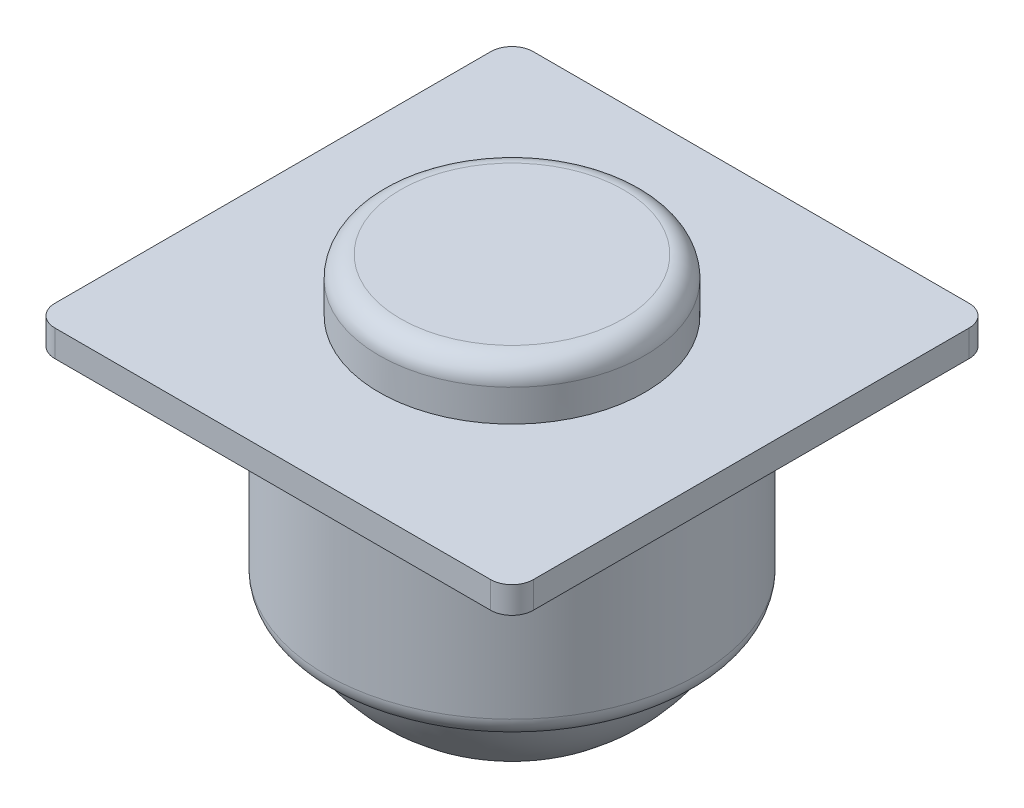
SolidWorks part; units mm, degrees
ref_plane "Front Plane" through (0, 0, 0) normal (0, 0, 1) x (1, 0, 0)
ref_plane "Top Plane" through (0, 0, 0) normal (0, 1, 0) x (1, 0, 0)
ref_plane "Right Plane" through (0, 0, 0) normal (1, 0, 0) x (0, 0, -1)
sketch "Sketch1" plane through (0, 0, 0) normal (0, 1, 0) x (1, 0, 0)
  line L1 (-14.2875, -14.2875) -> (14.2875, -14.2875)
  line L2 (-14.2875, -14.2875) -> (-14.2875, 14.2875)
  line L3 (-14.2875, 14.2875) -> (14.2875, 14.2875)
  line L4 (14.2875, -14.2875) -> (14.2875, 14.2875)
  line L5 (-14.2875, -14.2875) -> (14.2875, 14.2875) construction
  line L6 (-14.2875, 14.2875) -> (14.2875, -14.2875) construction
  point P0 (0, 0)
  dimension "D1" = 28.575
extrude "Boss-Extrude1" add sketch "Sketch1" along normal blind 1.5875
sketch "Sketch2" plane through (0, 1.5875, 0) normal (0, 1, 0) x (1, 0, 0)
  circle A0 centre (0, 0) radius 7.9375
  dimension "D1" = 15.875
extrude "Boss-Extrude2" add sketch "Sketch2" along normal blind 3.175
sketch "Sketch3" plane through (0, 0, 0) normal (0, -1, 0) x (1, 0, 0)
  circle A0 centre (0, 0) radius 11.1125
  dimension "D1" = 22.225
extrude "Boss-Extrude3" add sketch "Sketch3" along normal blind 12.7
fillet "Fillet1" radius 1.27 2 edges at (0, -12.7, -11.1125) (0, 4.7625, 7.9375)
dome "Dome1" faces to dome 1 distance 6.35 reverse direction no elliptical dome no face at (0, -12.7, -9.8425) parameters "D1"=6.35
fillet "Fillet2" radius 1.27 4 edges at (-14.2875, 0.7937, -14.2875) (14.2875, 0.7937, -14.2875) (14.2875, 0.7937, 14.2875) (-14.2875, 0.7937, 14.2875)
